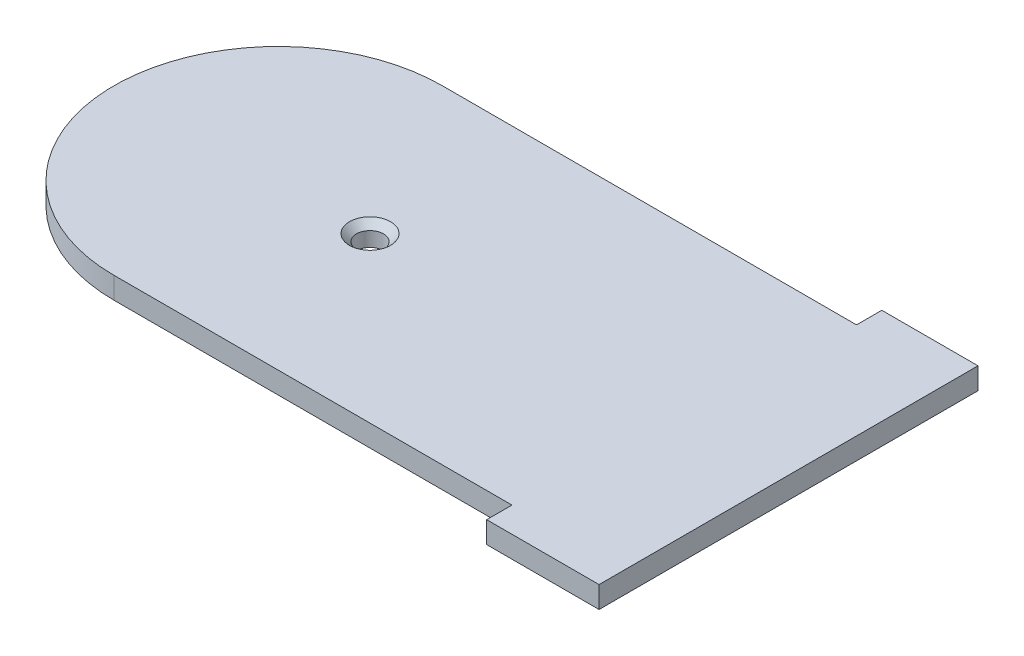
SolidWorks part; units mm, degrees
ref_plane "Front Plane" through (0, 0, 0) normal (0, 0, 1) x (1, 0, 0)
ref_plane "Top Plane" through (0, 0, 0) normal (0, 1, 0) x (1, 0, 0)
ref_plane "Right Plane" through (0, 0, 0) normal (1, 0, 0) x (0, 0, -1)
sketch "Base Shape Sketch" plane through (0, 0, 0) normal (0, 1, 0) x (1, 0, 0)
  line L0 (0, 15.19) -> (38.325, 15.19)
  line L2 (0, -15.19) -> (36.825, -15.19)
  line L5 (38.325, 15.19) -> (38.325, 17.5294)
  line L6 (38.325, 17.5294) -> (47.225, 17.5294)
  line L11 (47.225, -17.5294) -> (36.825, -17.5294)
  line L12 (36.825, -15.19) -> (36.825, -17.5294)
  line L14 (47.225, 17.5294) -> (47.225, -17.5294)
  arc A0 (0, 15.19) -> (0, -15.19) centre (0, 0) ccw
  dimension "D1" = 30.38
  dimension "D2" = 35.0589
  dimension "D3" = 2.3394
  dimension "D4" = 38.325
  dimension "D5" = 36.825
  dimension "D6" = 10.4
extrude "Base Shape" add sketch "Base Shape Sketch" along normal blind 2 contours L2 L12 L11 L14 L6 L5 L0 A0
sketch "Screw Hole Sketch" plane through (0, 2, 0) normal (0, 1, 0) x (1, 0, 0)
  circle A0 centre (8.5, 0) radius 1.25
  dimension "D1" = 2.5
  dimension "D2" = 8.5
extrude "Screw Hole" cut sketch "Screw Hole Sketch" against normal through all
sketch "Countersink Sketch" plane through (0, 0, 0) normal (0, 0, 1) x (1, 0, 0)
  line L0 (8.5, 2) -> (8.5, 0.8)
  line L1 (0, 2) -> (36.825, 2) construction
  line L2 (8.5, 0.8) -> (9.5, 0.8)
  line L3 (9.5, 0.8) -> (9.5, 1.1)
  line L4 (9.5, 1.1) -> (10.4, 2)
  line L5 (10.4, 2) -> (8.5, 2)
  dimension "D1" = 1.9
  dimension "D2" = 1.2
  dimension "D3" = 1
  dimension "D4" = 45
  dimension "D5" = 8.5
revolve "Screw Hole Countersink" cut sketch "Countersink Sketch" angle 360 about L0
sketch "PCB Cutout Sketch" plane through (0, 0, 0) normal (0, -1, 0) x (1, 0, 0)
  line L0 (-1.8189, -4.5) -> (-1.8189, 4.5) construction
  line L5 (-4.5, -6.5) -> (4.5, -6.5)
  line L6 (-4.5, -6.5) -> (-4.5, 4.5)
  line L7 (-4.5, 4.5) -> (4.5, 4.5)
  line L8 (4.5, -6.5) -> (4.5, 4.5)
  point P4 (0, -6.5)
  point P9 (-1.8189, 0)
  dimension "D1" = 11
  dimension "D2" = 9
  dimension "D3" = 9
extrude "Camera PCB Cutout" cut sketch "PCB Cutout Sketch" against normal blind 1.5
sketch "Ribbon Routing Sketch" plane through (4.5, 0, 0) normal (-1, 0, 0) x (0, 0, 1)
  line L0 (-6.5, 1.5) -> (-12.0981, 0)
  line L1 (-12.0981, 0) -> (-6.5, 0)
  line L2 (-6.5, 0) -> (-6.5, 1.5)
  dimension "D1" = 75
extrude "Camera Ribbon Routing" cut sketch "Ribbon Routing Sketch" along normal up to surface (9 mm away) up to face at (-4.5, 0.75, -1)
